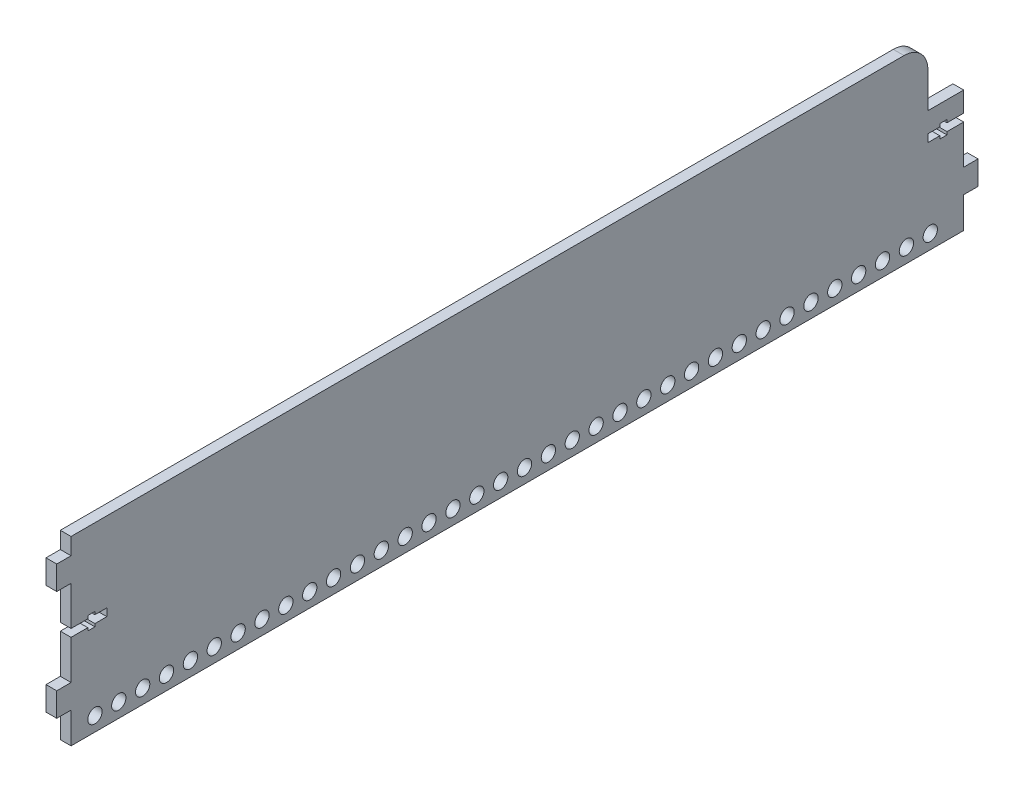
SolidWorks part; units mm, degrees
ref_plane "Front Plane" through (0, 0, 0) normal (0, 0, 1) x (1, 0, 0)
ref_plane "Top Plane" through (0, 0, 0) normal (0, 1, 0) x (1, 0, 0)
ref_plane "Right Plane" through (0, 0, 0) normal (1, 0, 0) x (0, 0, -1)
sketch "Sketch1" plane through (0, 0, 0) normal (1, 0, 0) x (0, 0, -1)
  line L1 (-187, -40) -> (187, -40)
  line L2 (-187, -40) -> (-187, 40)
  line L3 (-187, 40) -> (187, 40)
  line L4 (187, -40) -> (187, 40)
  line L5 (-187, -40) -> (187, 40) construction
  line L6 (-187, 40) -> (187, -40) construction
  point P0 (0, 0)
  dimension "D1" = 80
  dimension "D2" = 374
extrude "Boss-Extrude1" add sketch "Sketch1" along normal blind 4.5
sketch "Sketch4" plane through (0, 0, 187) normal (0, 0, 1) x (1, 0, 0)
  line L1 (4.5, 29) -> (0, 29) construction
  line L2 (4.5, 19) -> (4.5, 29) construction
  line L3 (0, 29) -> (0, 19) construction
  line L4 (0, 19) -> (4.5, 19) construction
  line L7 (4.5, -17) -> (0, -17) construction
  line L8 (4.5, -27) -> (4.5, -17) construction
  line L9 (0, -17) -> (0, -27) construction
  line L10 (0, -27) -> (4.5, -27) construction
  line L13 (4.5, 29) -> (0, 29)
  line L14 (4.5, 19) -> (4.5, 29)
  line L15 (0, 29) -> (0, 19)
  line L16 (0, 19) -> (4.5, 19)
  line L17 (4.5, -17) -> (0, -17)
  line L18 (4.5, -27) -> (4.5, -17)
  line L19 (0, -17) -> (0, -27)
  line L20 (0, -27) -> (4.5, -27)
extrude "Boss-Extrude2" add sketch "Sketch4" along normal blind 6
sketch "Sketch5" plane through (0, 0, 0) normal (-1, 0, 0) x (0, 0, 1)
  line L0 (187, 19) -> (187, -17) construction
  line L7 (0, 0) -> (0, -20.5925) construction
  line L8 (-187, 2.6) -> (-180, 2.6)
  line L9 (-177, 3.8) -> (-180, 3.8)
  line L10 (-177, 2.6) -> (-172, 2.6)
  line L11 (-172, -0.6) -> (-172, 2.6)
  line L12 (-177, -0.6) -> (-172, -0.6)
  line L13 (-177, -1.8) -> (-180, -1.8)
  line L14 (-187, -0.6) -> (-180, -0.6)
  line L15 (-180, -1.8) -> (-180, -0.6)
  line L16 (-180, 2.6) -> (-180, 3.8)
  line L17 (-177, 2.6) -> (-177, 3.8)
  line L18 (-177, -1.8) -> (-177, -0.6)
  line L19 (193, -0.6) -> (193, 2.6) construction
  line L20 (193, -0.6) -> (193, 2.6)
  line L21 (193, 1) -> (146.4296, 1) construction
  line L25 (187, -0.6) -> (187, 2.6)
  line L26 (177, -1.8) -> (177, -0.6)
  line L27 (177, 2.6) -> (177, 3.8)
  line L28 (180, 2.6) -> (180, 3.8)
  line L29 (180, -1.8) -> (180, -0.6)
  line L30 (187, -0.6) -> (180, -0.6)
  line L31 (177, -1.8) -> (180, -1.8)
  line L32 (177, -0.6) -> (172, -0.6)
  line L33 (172, -0.6) -> (172, 2.6)
  line L34 (177, 2.6) -> (172, 2.6)
  line L35 (177, 3.8) -> (180, 3.8)
  line L36 (187, 2.6) -> (180, 2.6)
  line L37 (-187, -0.6) -> (-187, 2.6)
  line L38 (-193, -0.6) -> (-193, 2.6)
  point P0 (187, 1)
  dimension "D1" = 15
  dimension "D2" = 5.6
  dimension "D3" = 3.2
  dimension "D4" = 7
  dimension "D5" = 3
extrude "Cut-Extrude3" cut sketch "Sketch5" against normal up to next contours L25 L36 L28 L35 L27 L34 L33 L32 L26 L31 L29 L30 | L37 L14 L15 L13 L18 L12 L11 L10 L17 L9 L16 L8 region at (0, 1, -179.3696) region at (0, 1, 179.3696)
sketch "Sketch7" plane through (0, 0, -187) normal (0, 0, -1) x (-1, 0, 0)
  line L6 (-4.5, -17) -> (0, -17)
  line L7 (-4.5, -17) -> (-4.5, -27)
  line L8 (-4.5, -27) -> (0, -27)
  line L9 (0, -17) -> (0, -27)
  line L15 (-4.5, -40) -> (-4.5, -0.6) construction
  line L16 (0, -40) -> (0, -0.6) construction
  line L17 (-4.5, -17) -> (0, -17) construction
  line L18 (0, -27) -> (-4.5, -27) construction
extrude "Boss-Extrude3" add sketch "Sketch7" along normal blind 6
sketch "Sketch8" plane through (0, 40, 0) normal (0, 1, 0) x (1, 0, 0)
  line L1 (0, 187) -> (4.5, 187)
  line L2 (0, 187) -> (0, -187)
  line L3 (0, -187) -> (4.5, -187)
  line L4 (4.5, 187) -> (4.5, -187)
extrude "Cut-Extrude4" cut sketch "Sketch8" against normal blind 4
sketch "Sketch9" plane through (0, 36, 0) normal (0, 1, 0) x (1, 0, 0)
  line L0 (0, 187) -> (0, -187) construction
  line L1 (0, 187) -> (4.5, 187)
  line L2 (0, 187) -> (0, 172)
  line L3 (0, 172) -> (4.5, 172)
  line L4 (4.5, 187) -> (4.5, 172)
  line L5 (4.5, -187) -> (4.5, 187) construction
  dimension "D2" = 15
extrude "Cut-Extrude5" cut sketch "Sketch9" against normal blind 25
fillet "Fillet1" radius 10 1 edges at (2.25, 36, -172)
sketch "Sketch10" plane through (0, 0, 0) normal (-1, 0, 0) x (0, 0, 1)
  line L0 (187, -40) -> (-187, -40) construction
  line L1 (187, -27) -> (187, -40) construction
  circle A0 centre (177, -34) radius 3
  circle A1 centre (167, -34) radius 3
  circle A2 centre (157, -34) radius 3
  circle A3 centre (147, -34) radius 3
  circle A4 centre (137, -34) radius 3
  circle A5 centre (127, -34) radius 3
  circle A6 centre (117, -34) radius 3
  circle A7 centre (107, -34) radius 3
  circle A8 centre (97, -34) radius 3
  circle A9 centre (87, -34) radius 3
  circle A10 centre (77, -34) radius 3
  circle A11 centre (67, -34) radius 3
  circle A12 centre (57, -34) radius 3
  circle A13 centre (47, -34) radius 3
  circle A14 centre (37, -34) radius 3
  circle A15 centre (27, -34) radius 3
  circle A16 centre (17, -34) radius 3
  circle A17 centre (7, -34) radius 3
  circle A18 centre (-3, -34) radius 3
  circle A19 centre (-13, -34) radius 3
  circle A20 centre (-23, -34) radius 3
  circle A21 centre (-33, -34) radius 3
  circle A22 centre (-43, -34) radius 3
  circle A23 centre (-53, -34) radius 3
  circle A24 centre (-63, -34) radius 3
  circle A25 centre (-73, -34) radius 3
  circle A26 centre (-83, -34) radius 3
  circle A27 centre (-93, -34) radius 3
  circle A28 centre (-103, -34) radius 3
  circle A29 centre (-113, -34) radius 3
  circle A30 centre (-123, -34) radius 3
  circle A31 centre (-133, -34) radius 3
  circle A32 centre (-143, -34) radius 3
  circle A33 centre (-153, -34) radius 3
  circle A34 centre (-163, -34) radius 3
  circle A35 centre (-173, -34) radius 3
  dimension "D1" = 6
  dimension "D2" = 6
  dimension "D3" = 10
  dimension "D4" = 36
extrude "Cut-Extrude6" cut sketch "Sketch10" against normal up to next (4.5 mm away)
